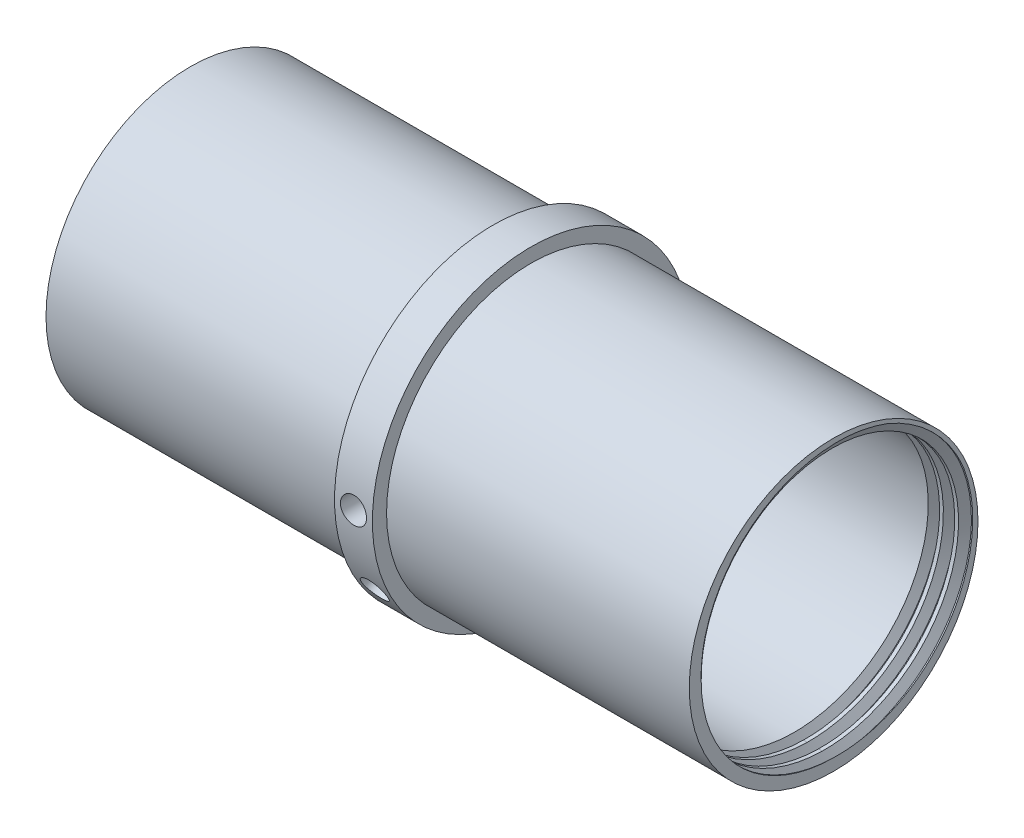
SolidWorks part; units mm, degrees
material "Custom Plastic"
ref_plane "Front Plane" through (0, 0, 0) normal (0, 0, 1) x (1, 0, 0)
ref_plane "Top Plane" through (0, 0, 0) normal (0, 1, 0) x (1, 0, 0)
ref_plane "Right Plane" through (0, 0, 0) normal (1, 0, 0) x (0, 0, -1)
sketch "Sketch1" plane through (0, 0, 0) normal (1, 0, 0) x (0, 0, -1)
  circle A0 centre (0, 0) radius 35
  circle A1 centre (0, 0) radius 38.15
  circle A2 centre (0, 0) radius 41.9
  dimension "D1" = 76.3
  dimension "D2" = 70
  dimension "D3" = 83.8
extrude "Boss-Extrude1" add sketch "Sketch1" along normal mid plane 170 contours A1 A0 region at (0, 0, 37.071)
extrude "Boss-Extrude2" add sketch "Sketch1<3>" along normal mid plane 10 contours A2 A1 region at (0, 0, 40.7149)
sketch "Sketch1<3>" plane through (0, 0, 0) normal (1, 0, 0) x (0, 0, -1) same geometry as "Sketch1"
thread "Thread2" pitch 4 method cut profile "Thread Profile2" start angle 0, offset 11, length 20, pitch 4, diameter 70
ref_plane "Plane2" through (96, 0, 35) normal (0, -1, 0) x (0, 0, 1)
sketch "Thread Profile2" plane through (96, 0, 35) normal (0, -1, 0) x (0, 0, 1)
  line L0 (0, 0) -> (0, 4) construction
  line L1 (0, 0) -> (2.1651, 1.25)
  line L2 (2.1651, 1.25) -> (2.1651, 1.75)
  line L3 (2.1651, 1.75) -> (0, 3)
  line L4 (2.1651, 1.5) -> (0, 1.5) construction
  line L11 (0, 0) -> (0, 3)
  point P2 (0, 0)
  dimension "Pitch" = 4
  dimension "Profile_Angle" = 60
  dimension "Profile_Land" = 0.5
  dimension "Profile_Height" = 2.1651
thread "Thread3" pitch 4 method cut profile "Thread Profile3" start angle 0, offset 11, length 20, pitch 4, diameter 70
ref_plane "Plane3" through (-96, 0, -35) normal (0, -1, 0) x (0, 0, -1)
sketch "Thread Profile3" plane through (-96, 0, -35) normal (0, -1, 0) x (0, 0, -1)
  line L0 (0, 0) -> (0, 4) construction
  line L1 (0, 0) -> (2.1651, 1.25)
  line L2 (2.1651, 1.25) -> (2.1651, 1.75)
  line L3 (2.1651, 1.75) -> (0, 3)
  line L4 (2.1651, 1.5) -> (0, 1.5) construction
  line L11 (0, 0) -> (0, 3)
  point P2 (0, 0)
  dimension "Pitch" = 4
  dimension "Profile_Angle" = 60
  dimension "Profile_Land" = 0.5
  dimension "Profile_Height" = 2.1651
ref_plane "Plane4" through (0, -41.9, 0) normal (0, -1, 0) x (-1, 0, 0)
sketch "Sketch2" plane through (0, -41.9, 0) normal (0, -1, 0) x (-1, 0, 0)
  circle A0 centre (0, 0) radius 3.45
  dimension "D1" = 6.9
extrude "Cut-Extrude1" cut sketch "Sketch2" against normal up to surface (7.0705 mm away)
ref_axis "Axis1" through (85, 0, 0) along (-1, 0, 0)
pattern_circular "CirPattern1" count 4 every 30 about axis through (85, 0, 0) along (-1, 0, 0) of "Cut-Extrude1"
